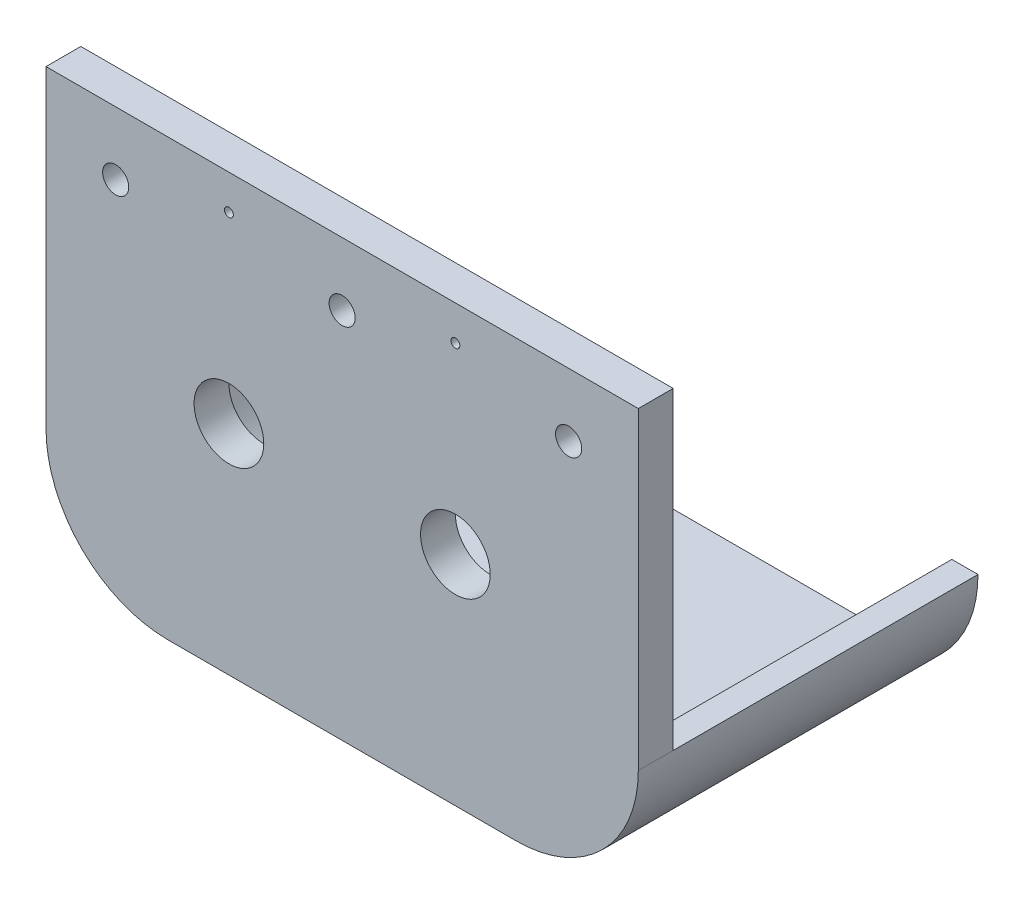
SolidWorks part; units mm, degrees
ref_plane "Front Plane" through (0, 0, 0) normal (0, 0, 1) x (1, 0, 0)
ref_plane "Top Plane" through (0, 0, 0) normal (0, 1, 0) x (1, 0, 0)
ref_plane "Right Plane" through (0, 0, 0) normal (1, 0, 0) x (0, 0, -1)
sketch "Sketch1" plane through (0, 0, 0) normal (0, 0, 1) x (1, 0, 0)
  line L0 (-1000, 0) -> (49000, 0) construction
  line L1 (-170, -125) -> (170, -125)
  line L2 (-170, -125) -> (-170, 125)
  line L3 (-170, 125) -> (170, 125)
  line L4 (170, -125) -> (170, 125)
  line L5 (-170, -125) -> (170, 125) construction
  line L6 (-170, 125) -> (170, -125) construction
  line L7 (0, -1000) -> (0, 49000) construction
  circle A0 centre (65, 0) radius 20
  circle A1 centre (-65, 0) radius 20
  point P0 (0, 0)
  dimension "D3" = 40
  dimension "D5" = 130
  dimension "D1" = 340
  dimension "D2" = 250
extrude "Boss-Extrude1" add sketch "Sketch1" along normal blind 20
sketch "Sketch2" plane through (0, 0, 20) normal (0, 0, 1) x (1, 0, 0)
  line L0 (0, -1000) -> (0, 49000) construction
  line L1 (-1000, 0) -> (49000, 0) construction
  line L2 (-1000, 88.7412) -> (49000, 88.7412) construction
  circle A0 centre (0, 88.7412) radius 7.5
  circle A2 centre (-130, 88.7412) radius 7.5
  circle A4 centre (130, 88.7412) radius 7.5
  circle A5 centre (65, 0) radius 20 construction
  circle A6 centre (-65, 0) radius 20 construction
  dimension "D1" = 15
  dimension "D2" = 110
  dimension "D3" = 110
extrude "Cut-Extrude1" cut sketch "Sketch2" against normal through all
fillet "Fillet1" radius 70 2 edges at (170, -125, 10) (-170, -125, 10)
sketch "Sketch3" plane through (0, 0, 0) normal (0, 0, -1) x (-1, 0, 0)
  line L1 (-170, -55) -> (-155, -55)
  line L2 (-100, -125) -> (100, -125)
  line L3 (0, -1000) -> (0, 49000) construction
  line L5 (-100, -110) -> (100, -110)
  line L8 (155, -55) -> (170, -55)
  arc A0 (100, -125) -> (170, -55) centre (100, -55) ccw construction
  arc A1 (-170, -55) -> (-100, -125) centre (-100, -55) ccw
  arc A2 (100, -125) -> (170, -55) centre (100, -55) ccw
  arc A5 (100, -110) -> (155, -55) centre (100, -55) ccw
  arc A6 (-155, -55) -> (-100, -110) centre (-100, -55) ccw
  arc M19 (-170, -55) -> (-100, -125) centre (-100, -55) ccw
  line M20 (-100, -125) -> (100, -125)
  arc M21 (100, -125) -> (170, -55) centre (100, -55) ccw
  dimension "D1" = 55
  dimension "D2" = 70
extrude "Boss-Extrude2" add sketch "Sketch3" along normal blind 175 contours L3 L5 A6 L1 M20 M19 | L3 L2 L8 A5 L5 M21 region at (162.5, -56.8385, 0) region at (-1.8385, -117.5, 0)
sketch "Sketch5" plane through (0, 0, -175) normal (0, 0, -1) x (-1, 0, 0)
  line L0 (0, -1000) -> (0, 49000) construction
  line L1 (-100, -110) -> (100, -110) construction
  line L3 (-1000, -117.5) -> (49000, -117.5) construction
  circle A0 centre (0, -117.5) radius 2.5
  circle A1 centre (70, -117.5) radius 2.5
  circle A2 centre (-70, -117.5) radius 2.5
  dimension "D1" = 5
  dimension "D3" = 70
  dimension "D2" = 7.5
extrude "Cut-Extrude2" cut sketch "Sketch5" against normal blind 30
fillet "Fillet2" radius 1 3 edges at (-72.5, -117.5, -145) (-2.5, -117.5, -145) (72.5, -117.5, -145)
fillet "Fillet3" radius 0.5 3 edges at (-72.5, -117.5, -175) (-2.5, -117.5, -175) (72.5, -117.5, -175)
sketch "Sketch6" plane through (0, 0, 0) normal (0, 0, -1) x (-1, 0, 0)
  line L0 (-1051.9004, 105) -> (48948.0996, 105) construction
  line L1 (-65, -1000) -> (-65, 49000) construction
  line L2 (65, -1000) -> (65, 49000) construction
  line L3 (-170, 125) -> (170, 125) construction
  circle A0 centre (65, 105) radius 5
  circle A1 centre (-65, 105) radius 5
  dimension "D2" = 10
  dimension "D1" = 20
hole_wizard "CSK for #10 Flat Head Machine Screw (100)2" positions "Sketch10" profile "Sketch11" countersink size "#10" standard "ANSI Inch"
sketch "Sketch10" plane through (0, 0, 0) normal (0, 0, -1) x (-1, 0, 0)
  point P0 (-65, 105)
  point P3 (65, 105)
sketch "Sketch11" plane through (65, 105, 0) normal (1, 0, 0) x (0, 1, 0)
  line L0 (0, 0) -> (0, 51.5338)
  line L1 (0, 51.5338) -> (2.5527, 50)
  line L2 (2.5527, 50) -> (2.5527, 1.9608)
  line L3 (2.5527, 1.9608) -> (4.8895, 0)
  line L5 (4.8895, 0) -> (0, 0)
  line L6 (-2.5527, 1.9608) -> (-4.8895, 0) construction
  line L10 (0, 51.5338) -> (-2.5527, 50) construction
  line L11 (0, -6.35) -> (0, 107.95) construction
  dimension "Hole Dia." = 5.1054
  dimension "Hole Depth" = 50
  dimension "Near C'Sink Dia." = 9.779
  dimension "Near C'Sink Angle" = 100
  dimension "Drill Angle" = 118
thread "Thread1" pitch 1.0583 method extrude profile "Thread Profile1" start angle 0, offset 0, length 10, pitch 1.0583, diameter 5.1054
ref_plane "Plane1" through (67.5527, 105, 1.9608) normal (0, -1, 0) x (1, 0, 0)
sketch "Thread Profile1" plane through (67.5527, 105, 1.9608) normal (0, -1, 0) x (1, 0, 0)
  line L0 (0, 0) -> (0, 1.0583) construction
  line L11 (0, 0) -> (0, 0.926)
  line L12 (0, 0.926) -> (-0.5728, 0.5953)
  line L13 (-0.5728, 0.5953) -> (-0.5728, 0.3307)
  line L15 (-0.5728, 0.3307) -> (0, 0)
  line L17 (-0.5728, 0.463) -> (0, 0.463) construction
  point P2 (0, 0)
  dimension "Pitch" = 1.0583
  dimension "Profile_Angle" = 60
  dimension "Profile_Land" = 0.2646
  dimension "Profile_Height" = 0.5728
thread "Thread2" pitch 1.0583 method extrude profile "Thread Profile2" start angle 0, offset 0, length 10, pitch 1.0583, diameter 5.1054
ref_plane "Plane2" through (-62.4473, 105, 1.9608) normal (0, -1, 0) x (1, 0, 0)
sketch "Thread Profile2" plane through (-62.4473, 105, 1.9608) normal (0, -1, 0) x (1, 0, 0)
  line L0 (0, 0) -> (0, 1.0583) construction
  line L11 (0, 0) -> (0, 0.926)
  line L12 (0, 0.926) -> (-0.5728, 0.5953)
  line L13 (-0.5728, 0.5953) -> (-0.5728, 0.3307)
  line L15 (-0.5728, 0.3307) -> (0, 0)
  line L17 (-0.5728, 0.463) -> (0, 0.463) construction
  point P2 (0, 0)
  dimension "Pitch" = 1.0583
  dimension "Profile_Angle" = 60
  dimension "Profile_Land" = 0.2646
  dimension "Profile_Height" = 0.5728
